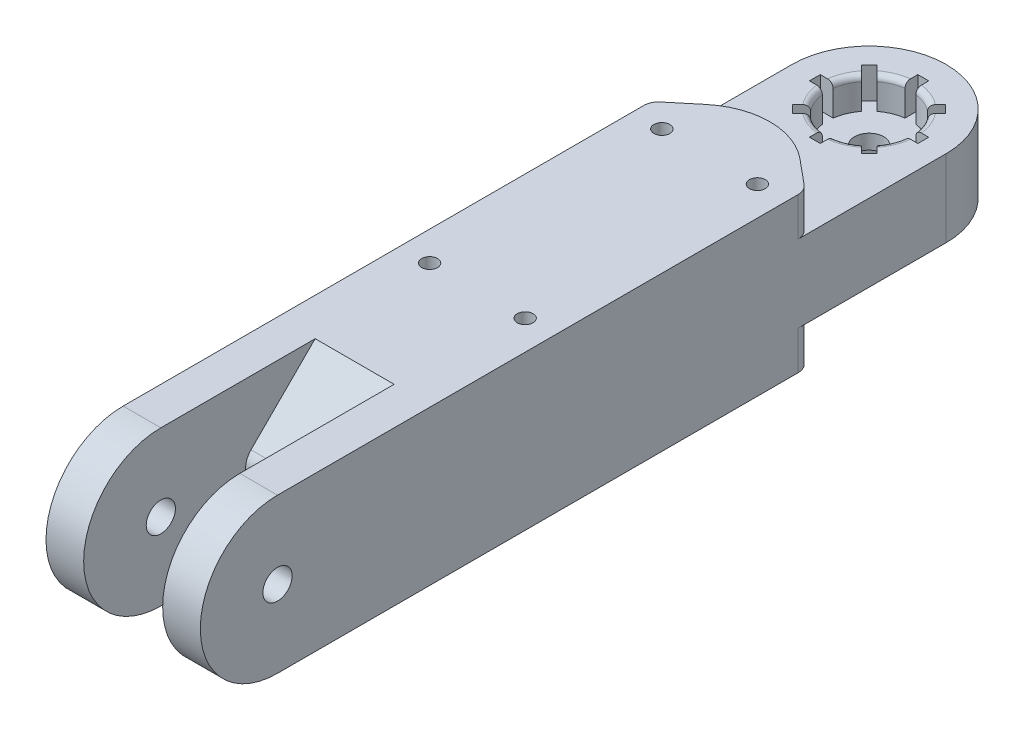
SolidWorks part; units mm, degrees
ref_plane "Front Plane" through (0, 0, 0) normal (0, 0, 1) x (1, 0, 0)
ref_plane "Top Plane" through (0, 0, 0) normal (0, 1, 0) x (1, 0, 0)
ref_plane "Right Plane" through (0, 0, 0) normal (1, 0, 0) x (0, 0, -1)
sketch "Sketch1" plane through (0, 0, 0) normal (0, 0, 1) x (1, 0, 0)
  line L1 (-21, 21) -> (21, 21)
  line L2 (-21, 21) -> (-21, -21)
  line L3 (-21, -21) -> (21, -21)
  line L4 (21, 21) -> (21, -21)
  line L5 (-21, 21) -> (21, -21) construction
  line L6 (-21, -21) -> (21, 21) construction
  point P0 (0, 0)
  dimension "D1" = 42
  dimension "D2" = 42
extrude "Boss-Extrude1" add sketch "Sketch1" along normal blind 140
ref_plane "Plane1" through (0, 0, 140) normal (0, 0, 1) x (1, 0, 0)
sketch "Sketch2" plane through (0, 0, 140) normal (0, 0, 1) x (1, 0, 0)
  line L0 (-21, -21) -> (21, -21) construction
  line L1 (-21, 21) -> (-10.75, 21)
  line L2 (-21, 21) -> (-21, -21)
  line L3 (-21, -21) -> (-10.75, -21)
  line L4 (-10.75, 21) -> (-10.75, -21)
  line L5 (21, 21) -> (-21, 21) construction
  line L6 (21, -21) -> (10.75, -21)
  line L7 (21, -21) -> (21, 21)
  line L8 (21, 21) -> (10.75, 21)
  line L9 (10.75, -21) -> (10.75, 21)
  dimension "D1" = 10.25
  dimension "D2" = 10.25
extrude "Boss-Extrude2" add sketch "Sketch2" along normal blind 21
ref_plane "Plane2" through (-10.75, 0, 0) normal (1, 0, 0) x (0, 0, -1)
sketch "Sketch3" plane through (-10.75, 0, 0) normal (1, 0, 0) x (0, 0, -1)
  line L0 (-161, -21) -> (-161, 21)
  arc A0 (-161, -21) -> (-161, 21) centre (-161, 0) cw
  dimension "D1" = 21
ref_plane "Plane3" through (0, -21, 0) normal (0, -1, 0) x (-1, 0, 0)
ref_plane "Plane4" through (10.75, 0, 0) normal (-1, 0, 0) x (0, 0, 1)
sketch "Sketch5" plane through (10.75, 0, 0) normal (-1, 0, 0) x (0, 0, 1)
  line L0 (161, 21) -> (161, -21)
  line L4 (140, 21) -> (140, -21)
  line L5 (140, -21) -> (161, -21)
  line L6 (161, -21) -> (161, 21)
  line L7 (161, 21) -> (140, 21)
  line L8 (140, 21) -> (140, -21)
  line L9 (140, -21) -> (161, -21)
  line L11 (161, 21) -> (140, 21)
  arc A0 (161, 21) -> (161, -21) centre (161, 0) cw
  dimension "D1" = 21
  dimension "D2" = 0
extrude "Boss-Extrude4" add sketch "Sketch5" against normal blind 10.25 contours A0 L0 region at (10.75, 0, 169.9127)
extrude "Boss-Extrude5" add sketch "Sketch3" against normal blind 10.25
sketch "Sketch6" plane through (10.75, 0, 0) normal (-1, 0, 0) x (0, 0, 1)
  line L0 (161, -21) -> (161, 21) construction
  circle A0 centre (161, 0) radius 3.975
  dimension "D1" = 7.95
extrude "Cut-Extrude1" cut sketch "Sketch6" against normal through all
ref_plane "Plane5" through (-10.75, 0, 0) normal (1, 0, 0) x (0, 0, -1)
sketch "Sketch8" plane through (-10.75, 0, 0) normal (1, 0, 0) x (0, 0, -1)
  line L0 (-161, -21) -> (-161, 21) construction
  circle A0 centre (-161, 0) radius 3.975
  dimension "D1" = 7.95
extrude "Cut-Extrude2" cut sketch "Sketch8" against normal through all
ref_plane "Plane6" through (0, 0, 0) normal (0, 0, -1) x (-1, 0, 0)
sketch "Sketch9" plane through (0, 0, 0) normal (0, 0, -1) x (-1, 0, 0)
  line L0 (21, 21) -> (21, -21) construction
  line L1 (21, 10.5) -> (-21, 10.5)
  line L2 (21, 10.5) -> (21, -10.5)
  line L3 (21, -10.5) -> (-21, -10.5)
  line L4 (-21, 10.5) -> (-21, -10.5)
  line L5 (-21, -21) -> (-21, 21) construction
  line L6 (-21, 21) -> (21, 21) construction
  line L7 (21, -21) -> (-21, -21) construction
  dimension "D1" = 10.5
  dimension "D2" = 10.5
extrude "Boss-Extrude6" add sketch "Sketch9" along normal blind 21
ref_plane "Plane7" through (0, -10.5, 0) normal (0, -1, 0) x (-1, 0, 0)
sketch "Sketch10" plane through (0, -10.5, 0) normal (0, -1, 0) x (-1, 0, 0)
  line L0 (-21, 21) -> (21, 21)
  arc A0 (-21, 21) -> (21, 21) centre (0, 21) cw
  dimension "D1" = 21
extrude "Boss-Extrude7" add sketch "Sketch10" against normal blind 21
sketch "Sketch11" plane through (0, -10.5, 0) normal (0, -1, 0) x (-1, 0, 0)
  line L0 (21, 21) -> (-21, 21) construction
  circle A0 centre (0, 21) radius 11.35
  dimension "D1" = 22.7
extrude "Cut-Extrude3" cut sketch "Sketch11" against normal blind 8.5
ref_plane "Plane8" through (10.75, 0, 0) normal (-1, 0, 0) x (0, 0, 1)
sketch "Sketch16" plane through (10.75, 0, 0) normal (-1, 0, 0) x (0, 0, 1)
  line L0 (140, 21) -> (140, 0)
  line L1 (140, 21) -> (140, -21) construction
  line L2 (140, 0) -> (140, -21)
  line L3 (140, -21) -> (119, -21)
  line L4 (119, -21) -> (140, 0)
  line L5 (140, 21) -> (119, 21)
  line L6 (119, 21) -> (140, 0)
  line L7 (161, 0) -> (140, 0) construction
  dimension "D1" = 21
  dimension "D2" = 21
extrude "Cut-Extrude4" cut sketch "Sketch16" along normal blind 21.5 contours L0 L5 L6 | L2 L3 L4
fillet "Fillet1" radius 5 1 edges at (0, 0, 140)
ref_plane "Plane9" through (0, -10.5, 0) normal (0, -1, 0) x (-1, 0, 0)
ref_plane "Plane10" through (0, 10.5, 0) normal (0, 1, 0) x (1, 0, 0)
sketch "Sketch18" plane through (0, 10.5, 0) normal (0, 1, 0) x (1, 0, 0)
  line L0 (21, 21) -> (-21, 21) construction
  circle A0 centre (0, 21) radius 11.35
  dimension "D1" = 22.7
extrude "Cut-Extrude5" cut sketch "Sketch18" against normal blind 8.5
sketch "Sketch19" plane through (0, -2, 0) normal (0, -1, 0) x (1, 0, 0)
  circle A0 centre (0, -21) radius 3.975
  dimension "D1" = 7.95
extrude "Cut-Extrude6" cut sketch "Sketch19" against normal blind 8.5
fillet "Fillet4" radius 1.5 1 edges at (11.35, -10.5, -21)
fillet "Fillet5" radius 1.5 1 edges at (-11.35, 10.5, -21)
sketch "Sketch20" plane through (0, 10.5, 0) normal (0, 1, 0) x (1, 0, 0)
  line L1 (-1.48, 35.755) -> (1.48, 35.755)
  line L2 (-1.48, 35.755) -> (-1.48, 31.945)
  line L3 (-1.48, 31.945) -> (1.48, 31.945)
  line L4 (1.48, 35.755) -> (1.48, 31.945)
  line L5 (-1.48, 35.755) -> (1.48, 31.945) construction
  line L6 (-1.48, 31.945) -> (1.48, 35.755) construction
  circle A0 centre (0, 21) radius 12.85 construction
  point P0 (0, 33.85)
  dimension "D1" = 2.96
  dimension "D2" = 3.81
extrude "Cut-Extrude7" cut sketch "Sketch20" against normal blind 8.5
pattern_circular "CirPattern1" count 8 over 360 about axis through (0, 2, -21) along (0, 1, 0) of "Cut-Extrude7"
ref_plane "Plane11" through (0, 0, 0) normal (0, 1, 0) x (1, 0, 0)
mirror "Mirror1" about plane through (0, 0, 0) normal (0, 1, 0) of "CirPattern1"
sketch "Sketch25" plane through (0, -21, 0) normal (0, -1, 0) x (1, 0, 0)
  line L0 (0, 0) -> (0, 119) construction
  line L1 (-10.75, 119) -> (10.75, 119) construction
  line L2 (-21, 0) -> (21, 0) construction
  line L3 (17, 78.5) -> (-17, 78.5)
  line L4 (17, 78.5) -> (17, 29.5)
  line L5 (17, 29.5) -> (-17, 29.5)
  line L6 (-17, 78.5) -> (-17, 29.5)
  line L7 (17, 78.5) -> (-17, 29.5) construction
  line L8 (17, 29.5) -> (-17, 78.5) construction
  point P5 (0, 54)
  point P10 (0, 0)
  point P11 (0, 29.7886)
  point P12 (0, 0)
  point P13 (0, 0)
  point P14 (0, 38.1926)
  point P15 (0, 0)
  point P18 (0, 0)
  point P19 (0, 35.617)
  point P20 (0, 0)
  point P21 (0, 31.9463)
  dimension "D1" = 34
  dimension "D2" = 49
  dimension "D3" = 54
extrude "Cut-Extrude11" cut sketch "Sketch25" against normal blind 32 contours L3 L6 L5 L4 region at (0, -21, 54)
sketch "Sketch26" plane through (0, -21, 0) normal (0, -1, 0) x (1, 0, 0)
  line L0 (0, 29.5) -> (0, 18.4) construction
  line L1 (17, 29.5) -> (-17, 29.5)
  line L2 (17, 29.5) -> (17, 26.5)
  line L3 (17, 26.5) -> (-17, 26.5)
  line L4 (-17, 29.5) -> (-17, 26.5)
  line L5 (-17, 26.5) -> (17, 26.5)
  line L6 (-17, 26.5) -> (-17, 18.4)
  line L7 (-17, 18.4) -> (17, 18.4)
  line L8 (17, 26.5) -> (17, 18.4)
  line M6 (17, 29.5) -> (-17, 29.5)
  line M7 (-21, 0) -> (21, 0)
  dimension "D1" = 3
  dimension "D2" = 8.1
extrude "Cut-Extrude12" cut sketch "Sketch26" against normal blind 27 contours L3 L0 L8 M7 | L0 L3 L2 M6 | L0 L1 L4 L5 | L0 L5 L6 M7 | L0 L6 L7 M7 | L0 L7 L8 M7 region at (8.5, -21, 28) region at (-8.5, -21, 28) region at (8.5, -21, 22.45) region at (-8.5, -21, 22.45)
sketch "Sketch30" plane through (0, 6, 0) normal (0, -1, 0) x (1, 0, 0)
  line L0 (0, 29.5) -> (0, 18.4) construction
  line L1 (17, 29.5) -> (-17, 29.5) construction
  line L2 (-17, 18.4) -> (17, 18.4) construction
  line L3 (-17, 29.5) -> (-17, 18.4) construction
  circle A0 centre (-13, 22.4) radius 4
  circle A1 centre (-13, 22.4) radius 2.15
  dimension "D1" = 8
  dimension "D2" = 4.3
extrude "Cut-Extrude13" cut sketch "Sketch30" against normal through all contours A1 region at (-13, 6, 22.4)
ref_plane "Plane12" through (0, 0, 0) normal (-1, 0, 0) x (0, 0, 1)
mirror "Mirror9" about plane through (0, 0, 0) normal (-1, 0, 0) of "Cut-Extrude13"
ref_plane "Plane13" through (0, 0, 54) normal (0, 0, 1) x (1, 0, 0)
sketch "Sketch32" plane through (0, 21, 0) normal (0, 1, 0) x (1, 0, 0)
  line L3 (0, 0) -> (0, -65.7087) construction
  line L4 (0, 17.6) -> (0, -17.6) construction
  line L10 (0, 0) -> (21, -17.4215)
  line L11 (21, -161) -> (21, 0) construction
  line L13 (-21, -161) -> (-21, 0) construction
  line L14 (-21, -17.4215) -> (0, 0)
  line L15 (0, 0) -> (-21, 0)
  line L16 (-21, 0) -> (-21, -17.4215)
  line L17 (0, 0) -> (21, 0)
  line L18 (21, 0) -> (21, -17.4215)
  point P13 (21, -18.2986)
  point P14 (21, -17.4215)
  line M13 (21, -161) -> (21, 0)
  line M14 (21, 0) -> (-21, 0)
  line M15 (-21, 0) -> (-21, -161)
fillet "Fillet10" radius 3 2 edges at (-17, -7.5, 18.4) (17, -7.5, 18.4)
ref_plane "Plane14" through (0, 0, 54) normal (0, 0, -1) x (-1, 0, 0)
mirror "Mirror12" about plane through (0, 0, 54) normal (0, 0, -1) of "Fillet10", "Mirror9", "Cut-Extrude13", "Cut-Extrude12"
extrude "Cut-Extrude16" cut sketch "Sketch32" against normal blind 10.5 contours L14 M15 M14 | L10 M14 M13 region at (14, 21, 5.8072) region at (-14, 21, 5.8072)
fillet "Fillet12" radius 20 1 edges at (0, 15.75, 0)
mirror "Mirror13" about plane through (0, 0, 0) normal (0, 1, 0) of "Fillet12", "Cut-Extrude16"
fillet "Fillet13" radius 4 4 edges at (-21, 15.75, 17.4215) (-21, -15.75, 17.4215) (21, -15.75, 17.4215) (21, 15.75, 17.4215)
